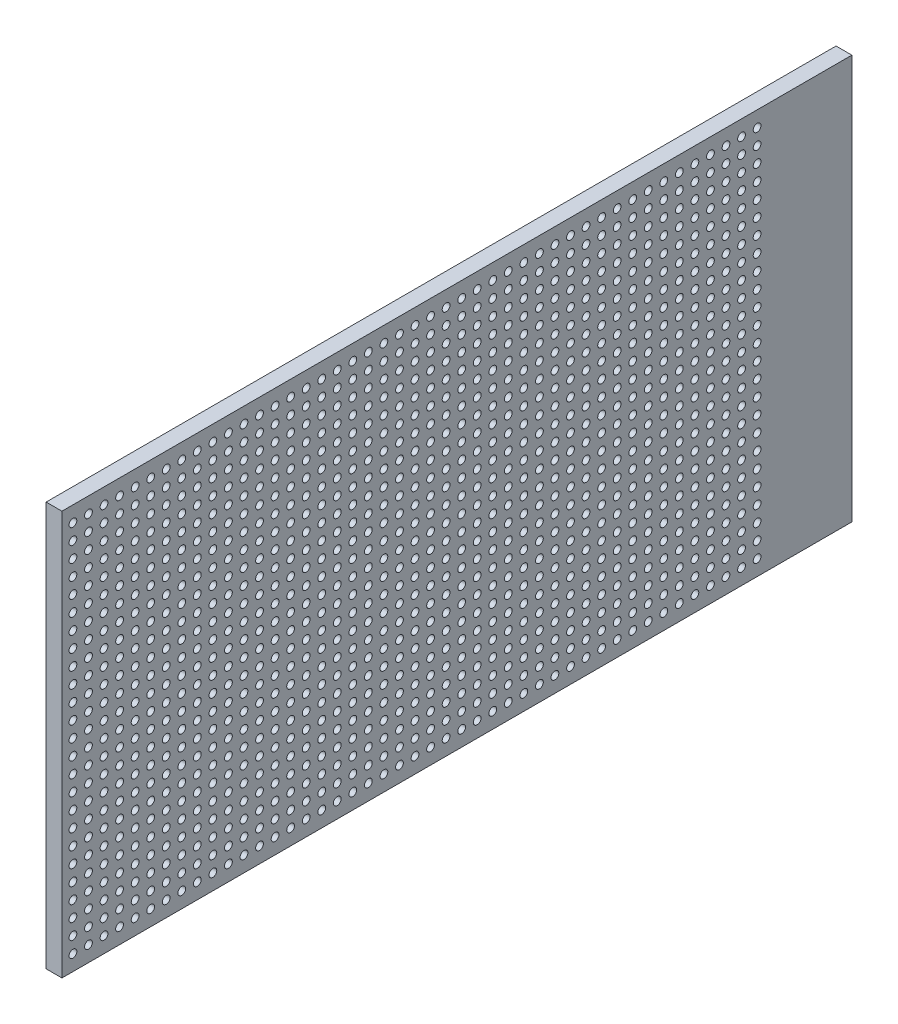
SolidWorks part; units mm, degrees
ref_plane "Спереди" through (0, 0, 0) normal (0, 0, 1) x (1, 0, 0)
ref_plane "Сверху" through (0, 0, 0) normal (0, 1, 0) x (1, 0, 0)
ref_plane "Справа" through (0, 0, 0) normal (1, 0, 0) x (0, 0, -1)
sketch "Эскиз2" plane through (0, 0, 0) normal (1, 0, 0) x (0, 0, -1)
  line L1 (1.4683, 0) -> (255.4683, 0)
  line L2 (1.4683, 0) -> (1.4683, 130)
  line L3 (1.4683, 130) -> (255.4683, 130)
  line L4 (255.4683, 0) -> (255.4683, 130)
  circle A0 centre (5, 5) radius 1.25
  circle A1 centre (10, 5) radius 1.25
  circle A2 centre (15, 5) radius 1.25
  circle A3 centre (20, 5) radius 1.25
  circle A4 centre (25, 5) radius 1.25
  circle A5 centre (30, 5) radius 1.25
  circle A6 centre (10, 10) radius 1.25
  circle A7 centre (15, 10) radius 1.25
  circle A8 centre (20, 10) radius 1.25
  circle A9 centre (25, 10) radius 1.25
  circle A10 centre (30, 10) radius 1.25
  circle A11 centre (10, 15) radius 1.25
  circle A12 centre (15, 15) radius 1.25
  circle A13 centre (20, 15) radius 1.25
  circle A14 centre (25, 15) radius 1.25
  circle A15 centre (30, 15) radius 1.25
  circle A16 centre (10, 20) radius 1.25
  circle A17 centre (15, 20) radius 1.25
  circle A18 centre (20, 20) radius 1.25
  circle A19 centre (25, 20) radius 1.25
  circle A20 centre (30, 20) radius 1.25
  circle A21 centre (10, 25) radius 1.25
  circle A22 centre (15, 25) radius 1.25
  circle A23 centre (20, 25) radius 1.25
  circle A24 centre (25, 25) radius 1.25
  circle A25 centre (30, 25) radius 1.25
  circle A26 centre (5, 10) radius 1.25
  circle A27 centre (5, 15) radius 1.25
  circle A28 centre (5, 20) radius 1.25
  circle A29 centre (5, 25) radius 1.25
  circle A30 centre (5, 30) radius 1.25
  circle A31 centre (10, 30) radius 1.25
  circle A32 centre (15, 30) radius 1.25
  circle A33 centre (20, 30) radius 1.25
  circle A34 centre (25, 30) radius 1.25
  circle A35 centre (30, 30) radius 1.25
  circle A36 centre (5, 35) radius 1.25
  circle A37 centre (10, 35) radius 1.25
  circle A38 centre (15, 35) radius 1.25
  circle A39 centre (20, 35) radius 1.25
  circle A40 centre (25, 35) radius 1.25
  circle A41 centre (30, 35) radius 1.25
  circle A42 centre (5, 40) radius 1.25
  circle A43 centre (10, 40) radius 1.25
  circle A44 centre (15, 40) radius 1.25
  circle A45 centre (20, 40) radius 1.25
  circle A46 centre (25, 40) radius 1.25
  circle A47 centre (30, 40) radius 1.25
  circle A48 centre (5, 45) radius 1.25
  circle A49 centre (10, 45) radius 1.25
  circle A50 centre (15, 45) radius 1.25
  circle A51 centre (20, 45) radius 1.25
  circle A52 centre (25, 45) radius 1.25
  circle A53 centre (30, 45) radius 1.25
  circle A54 centre (5, 50) radius 1.25
  circle A55 centre (10, 50) radius 1.25
  circle A56 centre (15, 50) radius 1.25
  circle A57 centre (20, 50) radius 1.25
  circle A58 centre (25, 50) radius 1.25
  circle A59 centre (30, 50) radius 1.25
  circle A60 centre (5, 55) radius 1.25
  circle A61 centre (10, 55) radius 1.25
  circle A62 centre (15, 55) radius 1.25
  circle A63 centre (20, 55) radius 1.25
  circle A64 centre (25, 55) radius 1.25
  circle A65 centre (30, 55) radius 1.25
  circle A66 centre (5, 60) radius 1.25
  circle A67 centre (10, 60) radius 1.25
  circle A68 centre (15, 60) radius 1.25
  circle A69 centre (20, 60) radius 1.25
  circle A70 centre (25, 60) radius 1.25
  circle A71 centre (30, 60) radius 1.25
  circle A72 centre (5, 65) radius 1.25
  circle A73 centre (10, 65) radius 1.25
  circle A74 centre (15, 65) radius 1.25
  circle A75 centre (20, 65) radius 1.25
  circle A76 centre (25, 65) radius 1.25
  circle A77 centre (30, 65) radius 1.25
  circle A78 centre (5, 70) radius 1.25
  circle A79 centre (10, 70) radius 1.25
  circle A80 centre (15, 70) radius 1.25
  circle A81 centre (20, 70) radius 1.25
  circle A82 centre (25, 70) radius 1.25
  circle A83 centre (30, 70) radius 1.25
  circle A84 centre (5, 75) radius 1.25
  circle A85 centre (10, 75) radius 1.25
  circle A86 centre (15, 75) radius 1.25
  circle A87 centre (20, 75) radius 1.25
  circle A88 centre (25, 75) radius 1.25
  circle A89 centre (30, 75) radius 1.25
  circle A90 centre (5, 80) radius 1.25
  circle A91 centre (10, 80) radius 1.25
  circle A92 centre (15, 80) radius 1.25
  circle A93 centre (20, 80) radius 1.25
  circle A94 centre (25, 80) radius 1.25
  circle A95 centre (30, 80) radius 1.25
  circle A96 centre (5, 85) radius 1.25
  circle A97 centre (10, 85) radius 1.25
  circle A98 centre (15, 85) radius 1.25
  circle A99 centre (20, 85) radius 1.25
  circle A100 centre (25, 85) radius 1.25
  circle A101 centre (30, 85) radius 1.25
  circle A102 centre (5, 90) radius 1.25
  circle A103 centre (10, 90) radius 1.25
  circle A104 centre (15, 90) radius 1.25
  circle A105 centre (20, 90) radius 1.25
  circle A106 centre (25, 90) radius 1.25
  circle A107 centre (30, 90) radius 1.25
  circle A108 centre (5, 95) radius 1.25
  circle A109 centre (10, 95) radius 1.25
  circle A110 centre (15, 95) radius 1.25
  circle A111 centre (20, 95) radius 1.25
  circle A112 centre (25, 95) radius 1.25
  circle A113 centre (30, 95) radius 1.25
  circle A114 centre (5, 100) radius 1.25
  circle A115 centre (10, 100) radius 1.25
  circle A116 centre (15, 100) radius 1.25
  circle A117 centre (20, 100) radius 1.25
  circle A118 centre (25, 100) radius 1.25
  circle A119 centre (30, 100) radius 1.25
  circle A120 centre (5, 105) radius 1.25
  circle A121 centre (10, 105) radius 1.25
  circle A122 centre (15, 105) radius 1.25
  circle A123 centre (20, 105) radius 1.25
  circle A124 centre (25, 105) radius 1.25
  circle A125 centre (30, 105) radius 1.25
  circle A126 centre (5, 110) radius 1.25
  circle A127 centre (10, 110) radius 1.25
  circle A128 centre (15, 110) radius 1.25
  circle A129 centre (20, 110) radius 1.25
  circle A130 centre (25, 110) radius 1.25
  circle A131 centre (30, 110) radius 1.25
  circle A132 centre (5, 115) radius 1.25
  circle A133 centre (10, 115) radius 1.25
  circle A134 centre (15, 115) radius 1.25
  circle A135 centre (20, 115) radius 1.25
  circle A136 centre (25, 115) radius 1.25
  circle A137 centre (30, 115) radius 1.25
  circle A138 centre (5, 120) radius 1.25
  circle A139 centre (10, 120) radius 1.25
  circle A140 centre (15, 120) radius 1.25
  circle A141 centre (20, 120) radius 1.25
  circle A142 centre (25, 120) radius 1.25
  circle A143 centre (30, 120) radius 1.25
  circle A144 centre (5, 125) radius 1.25
  circle A145 centre (10, 125) radius 1.25
  circle A146 centre (15, 125) radius 1.25
  circle A147 centre (20, 125) radius 1.25
  circle A148 centre (25, 125) radius 1.25
  circle A149 centre (30, 125) radius 1.25
  circle A150 centre (35, 5) radius 1.25
  circle A151 centre (40, 5) radius 1.25
  circle A152 centre (45, 5) radius 1.25
  circle A153 centre (50, 5) radius 1.25
  circle A154 centre (55, 5) radius 1.25
  circle A155 centre (60, 5) radius 1.25
  circle A156 centre (65, 5) radius 1.25
  circle A157 centre (70, 5) radius 1.25
  circle A158 centre (75, 5) radius 1.25
  circle A159 centre (80, 5) radius 1.25
  circle A160 centre (85, 5) radius 1.25
  circle A161 centre (90, 5) radius 1.25
  circle A162 centre (95, 5) radius 1.25
  circle A163 centre (100, 5) radius 1.25
  circle A164 centre (105, 5) radius 1.25
  circle A165 centre (110, 5) radius 1.25
  circle A166 centre (35, 10) radius 1.25
  circle A167 centre (40, 10) radius 1.25
  circle A168 centre (45, 10) radius 1.25
  circle A169 centre (50, 10) radius 1.25
  circle A170 centre (55, 10) radius 1.25
  circle A171 centre (60, 10) radius 1.25
  circle A172 centre (65, 10) radius 1.25
  circle A173 centre (70, 10) radius 1.25
  circle A174 centre (75, 10) radius 1.25
  circle A175 centre (80, 10) radius 1.25
  circle A176 centre (85, 10) radius 1.25
  circle A177 centre (90, 10) radius 1.25
  circle A178 centre (95, 10) radius 1.25
  circle A179 centre (100, 10) radius 1.25
  circle A180 centre (105, 10) radius 1.25
  circle A181 centre (110, 10) radius 1.25
  circle A182 centre (35, 15) radius 1.25
  circle A183 centre (40, 15) radius 1.25
  circle A184 centre (45, 15) radius 1.25
  circle A185 centre (50, 15) radius 1.25
  circle A186 centre (55, 15) radius 1.25
  circle A187 centre (60, 15) radius 1.25
  circle A188 centre (65, 15) radius 1.25
  circle A189 centre (70, 15) radius 1.25
  circle A190 centre (75, 15) radius 1.25
  circle A191 centre (80, 15) radius 1.25
  circle A192 centre (85, 15) radius 1.25
  circle A193 centre (90, 15) radius 1.25
  circle A194 centre (95, 15) radius 1.25
  circle A195 centre (100, 15) radius 1.25
  circle A196 centre (105, 15) radius 1.25
  circle A197 centre (110, 15) radius 1.25
  circle A198 centre (35, 20) radius 1.25
  circle A199 centre (40, 20) radius 1.25
  circle A200 centre (45, 20) radius 1.25
  circle A201 centre (50, 20) radius 1.25
  circle A202 centre (55, 20) radius 1.25
  circle A203 centre (60, 20) radius 1.25
  circle A204 centre (65, 20) radius 1.25
  circle A205 centre (70, 20) radius 1.25
  circle A206 centre (75, 20) radius 1.25
  circle A207 centre (80, 20) radius 1.25
  circle A208 centre (85, 20) radius 1.25
  circle A209 centre (90, 20) radius 1.25
  circle A210 centre (95, 20) radius 1.25
  circle A211 centre (100, 20) radius 1.25
  circle A212 centre (105, 20) radius 1.25
  circle A213 centre (110, 20) radius 1.25
  circle A214 centre (35, 25) radius 1.25
  circle A215 centre (40, 25) radius 1.25
  circle A216 centre (45, 25) radius 1.25
  circle A217 centre (50, 25) radius 1.25
  circle A218 centre (55, 25) radius 1.25
  circle A219 centre (60, 25) radius 1.25
  circle A220 centre (65, 25) radius 1.25
  circle A221 centre (70, 25) radius 1.25
  circle A222 centre (75, 25) radius 1.25
  circle A223 centre (80, 25) radius 1.25
  circle A224 centre (85, 25) radius 1.25
  circle A225 centre (90, 25) radius 1.25
  circle A226 centre (95, 25) radius 1.25
  circle A227 centre (100, 25) radius 1.25
  circle A228 centre (105, 25) radius 1.25
  circle A229 centre (110, 25) radius 1.25
  circle A230 centre (35, 30) radius 1.25
  circle A231 centre (40, 30) radius 1.25
  circle A232 centre (45, 30) radius 1.25
  circle A233 centre (50, 30) radius 1.25
  circle A234 centre (55, 30) radius 1.25
  circle A235 centre (60, 30) radius 1.25
  circle A236 centre (65, 30) radius 1.25
  circle A237 centre (70, 30) radius 1.25
  circle A238 centre (75, 30) radius 1.25
  circle A239 centre (80, 30) radius 1.25
  circle A240 centre (85, 30) radius 1.25
  circle A241 centre (90, 30) radius 1.25
  circle A242 centre (95, 30) radius 1.25
  circle A243 centre (100, 30) radius 1.25
  circle A244 centre (105, 30) radius 1.25
  circle A245 centre (110, 30) radius 1.25
  circle A246 centre (35, 35) radius 1.25
  circle A247 centre (40, 35) radius 1.25
  circle A248 centre (45, 35) radius 1.25
  circle A249 centre (50, 35) radius 1.25
  circle A250 centre (55, 35) radius 1.25
  circle A251 centre (60, 35) radius 1.25
  circle A252 centre (65, 35) radius 1.25
  circle A253 centre (70, 35) radius 1.25
  circle A254 centre (75, 35) radius 1.25
  circle A255 centre (80, 35) radius 1.25
  circle A256 centre (85, 35) radius 1.25
  circle A257 centre (90, 35) radius 1.25
  circle A258 centre (95, 35) radius 1.25
  circle A259 centre (100, 35) radius 1.25
  circle A260 centre (105, 35) radius 1.25
  circle A261 centre (110, 35) radius 1.25
  circle A262 centre (35, 40) radius 1.25
  circle A263 centre (40, 40) radius 1.25
  circle A264 centre (45, 40) radius 1.25
  circle A265 centre (50, 40) radius 1.25
  circle A266 centre (55, 40) radius 1.25
  circle A267 centre (60, 40) radius 1.25
  circle A268 centre (65, 40) radius 1.25
  circle A269 centre (70, 40) radius 1.25
  circle A270 centre (75, 40) radius 1.25
  circle A271 centre (80, 40) radius 1.25
  circle A272 centre (85, 40) radius 1.25
  circle A273 centre (90, 40) radius 1.25
  circle A274 centre (95, 40) radius 1.25
  circle A275 centre (100, 40) radius 1.25
  circle A276 centre (105, 40) radius 1.25
  circle A277 centre (110, 40) radius 1.25
  circle A278 centre (35, 45) radius 1.25
  circle A279 centre (40, 45) radius 1.25
  circle A280 centre (45, 45) radius 1.25
  circle A281 centre (50, 45) radius 1.25
  circle A282 centre (55, 45) radius 1.25
  circle A283 centre (60, 45) radius 1.25
  circle A284 centre (65, 45) radius 1.25
  circle A285 centre (70, 45) radius 1.25
  circle A286 centre (75, 45) radius 1.25
  circle A287 centre (80, 45) radius 1.25
  circle A288 centre (85, 45) radius 1.25
  circle A289 centre (90, 45) radius 1.25
  circle A290 centre (95, 45) radius 1.25
  circle A291 centre (100, 45) radius 1.25
  circle A292 centre (105, 45) radius 1.25
  circle A293 centre (110, 45) radius 1.25
  circle A294 centre (35, 50) radius 1.25
  circle A295 centre (40, 50) radius 1.25
  circle A296 centre (45, 50) radius 1.25
  circle A297 centre (50, 50) radius 1.25
  circle A298 centre (55, 50) radius 1.25
  circle A299 centre (60, 50) radius 1.25
  circle A300 centre (65, 50) radius 1.25
  circle A301 centre (70, 50) radius 1.25
  circle A302 centre (75, 50) radius 1.25
  circle A303 centre (80, 50) radius 1.25
  circle A304 centre (85, 50) radius 1.25
  circle A305 centre (90, 50) radius 1.25
  circle A306 centre (95, 50) radius 1.25
  circle A307 centre (100, 50) radius 1.25
  circle A308 centre (105, 50) radius 1.25
  circle A309 centre (110, 50) radius 1.25
  circle A310 centre (35, 55) radius 1.25
  circle A311 centre (40, 55) radius 1.25
  circle A312 centre (45, 55) radius 1.25
  circle A313 centre (50, 55) radius 1.25
  circle A314 centre (55, 55) radius 1.25
  circle A315 centre (60, 55) radius 1.25
  circle A316 centre (65, 55) radius 1.25
  circle A317 centre (70, 55) radius 1.25
  circle A318 centre (75, 55) radius 1.25
  circle A319 centre (80, 55) radius 1.25
  circle A320 centre (85, 55) radius 1.25
  circle A321 centre (90, 55) radius 1.25
  circle A322 centre (95, 55) radius 1.25
  circle A323 centre (100, 55) radius 1.25
  circle A324 centre (105, 55) radius 1.25
  circle A325 centre (110, 55) radius 1.25
  circle A326 centre (35, 60) radius 1.25
  circle A327 centre (40, 60) radius 1.25
  circle A328 centre (45, 60) radius 1.25
  circle A329 centre (50, 60) radius 1.25
  circle A330 centre (55, 60) radius 1.25
  circle A331 centre (60, 60) radius 1.25
  circle A332 centre (65, 60) radius 1.25
  circle A333 centre (70, 60) radius 1.25
  circle A334 centre (75, 60) radius 1.25
  circle A335 centre (80, 60) radius 1.25
  circle A336 centre (85, 60) radius 1.25
  circle A337 centre (90, 60) radius 1.25
  circle A338 centre (95, 60) radius 1.25
  circle A339 centre (100, 60) radius 1.25
  circle A340 centre (105, 60) radius 1.25
  circle A341 centre (110, 60) radius 1.25
  circle A342 centre (35, 65) radius 1.25
  circle A343 centre (40, 65) radius 1.25
  circle A344 centre (45, 65) radius 1.25
  circle A345 centre (50, 65) radius 1.25
  circle A346 centre (55, 65) radius 1.25
  circle A347 centre (60, 65) radius 1.25
  circle A348 centre (65, 65) radius 1.25
  circle A349 centre (70, 65) radius 1.25
  circle A350 centre (75, 65) radius 1.25
  circle A351 centre (80, 65) radius 1.25
  circle A352 centre (85, 65) radius 1.25
  circle A353 centre (90, 65) radius 1.25
  circle A354 centre (95, 65) radius 1.25
  circle A355 centre (100, 65) radius 1.25
  circle A356 centre (105, 65) radius 1.25
  circle A357 centre (110, 65) radius 1.25
  circle A358 centre (35, 70) radius 1.25
  circle A359 centre (40, 70) radius 1.25
  circle A360 centre (45, 70) radius 1.25
  circle A361 centre (50, 70) radius 1.25
  circle A362 centre (55, 70) radius 1.25
  circle A363 centre (60, 70) radius 1.25
  circle A364 centre (65, 70) radius 1.25
  circle A365 centre (70, 70) radius 1.25
  circle A366 centre (75, 70) radius 1.25
  circle A367 centre (80, 70) radius 1.25
  circle A368 centre (85, 70) radius 1.25
  circle A369 centre (90, 70) radius 1.25
  circle A370 centre (95, 70) radius 1.25
  circle A371 centre (100, 70) radius 1.25
  circle A372 centre (105, 70) radius 1.25
  circle A373 centre (110, 70) radius 1.25
  circle A374 centre (35, 75) radius 1.25
  circle A375 centre (40, 75) radius 1.25
  circle A376 centre (45, 75) radius 1.25
  circle A377 centre (50, 75) radius 1.25
  circle A378 centre (55, 75) radius 1.25
  circle A379 centre (60, 75) radius 1.25
  circle A380 centre (65, 75) radius 1.25
  circle A381 centre (70, 75) radius 1.25
  circle A382 centre (75, 75) radius 1.25
  circle A383 centre (80, 75) radius 1.25
  circle A384 centre (85, 75) radius 1.25
  circle A385 centre (90, 75) radius 1.25
  circle A386 centre (95, 75) radius 1.25
  circle A387 centre (100, 75) radius 1.25
  circle A388 centre (105, 75) radius 1.25
  circle A389 centre (110, 75) radius 1.25
  circle A390 centre (35, 80) radius 1.25
  circle A391 centre (40, 80) radius 1.25
  circle A392 centre (45, 80) radius 1.25
  circle A393 centre (50, 80) radius 1.25
  circle A394 centre (55, 80) radius 1.25
  circle A395 centre (60, 80) radius 1.25
  circle A396 centre (65, 80) radius 1.25
  circle A397 centre (70, 80) radius 1.25
  circle A398 centre (75, 80) radius 1.25
  circle A399 centre (80, 80) radius 1.25
  circle A400 centre (85, 80) radius 1.25
  circle A401 centre (90, 80) radius 1.25
  circle A402 centre (95, 80) radius 1.25
  circle A403 centre (100, 80) radius 1.25
  circle A404 centre (105, 80) radius 1.25
  circle A405 centre (110, 80) radius 1.25
  circle A406 centre (35, 85) radius 1.25
  circle A407 centre (40, 85) radius 1.25
  circle A408 centre (45, 85) radius 1.25
  circle A409 centre (50, 85) radius 1.25
  circle A410 centre (55, 85) radius 1.25
  circle A411 centre (60, 85) radius 1.25
  circle A412 centre (65, 85) radius 1.25
  circle A413 centre (70, 85) radius 1.25
  circle A414 centre (75, 85) radius 1.25
  circle A415 centre (80, 85) radius 1.25
  circle A416 centre (85, 85) radius 1.25
  circle A417 centre (90, 85) radius 1.25
  circle A418 centre (95, 85) radius 1.25
  circle A419 centre (100, 85) radius 1.25
  circle A420 centre (105, 85) radius 1.25
  circle A421 centre (110, 85) radius 1.25
  circle A422 centre (35, 90) radius 1.25
  circle A423 centre (40, 90) radius 1.25
  circle A424 centre (45, 90) radius 1.25
  circle A425 centre (50, 90) radius 1.25
  circle A426 centre (55, 90) radius 1.25
  circle A427 centre (60, 90) radius 1.25
  circle A428 centre (65, 90) radius 1.25
  circle A429 centre (70, 90) radius 1.25
  circle A430 centre (75, 90) radius 1.25
  circle A431 centre (80, 90) radius 1.25
  circle A432 centre (85, 90) radius 1.25
  circle A433 centre (90, 90) radius 1.25
  circle A434 centre (95, 90) radius 1.25
  circle A435 centre (100, 90) radius 1.25
  circle A436 centre (105, 90) radius 1.25
  circle A437 centre (110, 90) radius 1.25
  circle A438 centre (35, 95) radius 1.25
  circle A439 centre (40, 95) radius 1.25
  circle A440 centre (45, 95) radius 1.25
  circle A441 centre (50, 95) radius 1.25
  circle A442 centre (55, 95) radius 1.25
  circle A443 centre (60, 95) radius 1.25
  circle A444 centre (65, 95) radius 1.25
  circle A445 centre (70, 95) radius 1.25
  circle A446 centre (75, 95) radius 1.25
  circle A447 centre (80, 95) radius 1.25
  circle A448 centre (85, 95) radius 1.25
  circle A449 centre (90, 95) radius 1.25
  circle A450 centre (95, 95) radius 1.25
  circle A451 centre (100, 95) radius 1.25
  circle A452 centre (105, 95) radius 1.25
  circle A453 centre (110, 95) radius 1.25
  circle A454 centre (35, 100) radius 1.25
  circle A455 centre (40, 100) radius 1.25
  circle A456 centre (45, 100) radius 1.25
  circle A457 centre (50, 100) radius 1.25
  circle A458 centre (55, 100) radius 1.25
  circle A459 centre (60, 100) radius 1.25
  circle A460 centre (65, 100) radius 1.25
  circle A461 centre (70, 100) radius 1.25
  circle A462 centre (75, 100) radius 1.25
  circle A463 centre (80, 100) radius 1.25
  circle A464 centre (85, 100) radius 1.25
  circle A465 centre (90, 100) radius 1.25
  circle A466 centre (95, 100) radius 1.25
  circle A467 centre (100, 100) radius 1.25
  circle A468 centre (105, 100) radius 1.25
  circle A469 centre (110, 100) radius 1.25
  circle A470 centre (35, 105) radius 1.25
  circle A471 centre (40, 105) radius 1.25
  circle A472 centre (45, 105) radius 1.25
  circle A473 centre (50, 105) radius 1.25
  circle A474 centre (55, 105) radius 1.25
  circle A475 centre (60, 105) radius 1.25
  circle A476 centre (65, 105) radius 1.25
  circle A477 centre (70, 105) radius 1.25
  circle A478 centre (75, 105) radius 1.25
  circle A479 centre (80, 105) radius 1.25
  circle A480 centre (85, 105) radius 1.25
  circle A481 centre (90, 105) radius 1.25
  circle A482 centre (95, 105) radius 1.25
  circle A483 centre (100, 105) radius 1.25
  circle A484 centre (105, 105) radius 1.25
  circle A485 centre (110, 105) radius 1.25
  circle A486 centre (35, 110) radius 1.25
  circle A487 centre (40, 110) radius 1.25
  circle A488 centre (45, 110) radius 1.25
  circle A489 centre (50, 110) radius 1.25
  circle A490 centre (55, 110) radius 1.25
  circle A491 centre (60, 110) radius 1.25
  circle A492 centre (65, 110) radius 1.25
  circle A493 centre (70, 110) radius 1.25
  circle A494 centre (75, 110) radius 1.25
  circle A495 centre (80, 110) radius 1.25
  circle A496 centre (85, 110) radius 1.25
  circle A497 centre (90, 110) radius 1.25
  circle A498 centre (95, 110) radius 1.25
  circle A499 centre (100, 110) radius 1.25
  circle A500 centre (105, 110) radius 1.25
  circle A501 centre (110, 110) radius 1.25
  circle A502 centre (35, 115) radius 1.25
  circle A503 centre (40, 115) radius 1.25
  circle A504 centre (45, 115) radius 1.25
  circle A505 centre (50, 115) radius 1.25
  circle A506 centre (55, 115) radius 1.25
  circle A507 centre (60, 115) radius 1.25
  circle A508 centre (65, 115) radius 1.25
  circle A509 centre (70, 115) radius 1.25
  circle A510 centre (75, 115) radius 1.25
  circle A511 centre (80, 115) radius 1.25
  circle A512 centre (85, 115) radius 1.25
  circle A513 centre (90, 115) radius 1.25
  circle A514 centre (95, 115) radius 1.25
  circle A515 centre (100, 115) radius 1.25
  circle A516 centre (105, 115) radius 1.25
  circle A517 centre (110, 115) radius 1.25
  circle A518 centre (35, 120) radius 1.25
  circle A519 centre (40, 120) radius 1.25
  circle A520 centre (45, 120) radius 1.25
  circle A521 centre (50, 120) radius 1.25
  circle A522 centre (55, 120) radius 1.25
  circle A523 centre (60, 120) radius 1.25
  circle A524 centre (65, 120) radius 1.25
  circle A525 centre (70, 120) radius 1.25
  circle A526 centre (75, 120) radius 1.25
  circle A527 centre (80, 120) radius 1.25
  circle A528 centre (85, 120) radius 1.25
  circle A529 centre (90, 120) radius 1.25
  circle A530 centre (95, 120) radius 1.25
  circle A531 centre (100, 120) radius 1.25
  circle A532 centre (105, 120) radius 1.25
  circle A533 centre (110, 120) radius 1.25
  circle A534 centre (35, 125) radius 1.25
  circle A535 centre (40, 125) radius 1.25
  circle A536 centre (45, 125) radius 1.25
  circle A537 centre (50, 125) radius 1.25
  circle A538 centre (55, 125) radius 1.25
  circle A539 centre (60, 125) radius 1.25
  circle A540 centre (65, 125) radius 1.25
  circle A541 centre (70, 125) radius 1.25
  circle A542 centre (75, 125) radius 1.25
  circle A543 centre (80, 125) radius 1.25
  circle A544 centre (85, 125) radius 1.25
  circle A545 centre (90, 125) radius 1.25
  circle A546 centre (95, 125) radius 1.25
  circle A547 centre (100, 125) radius 1.25
  circle A548 centre (105, 125) radius 1.25
  circle A549 centre (110, 125) radius 1.25
  circle A550 centre (115, 5) radius 1.25
  circle A551 centre (120, 5) radius 1.25
  circle A552 centre (125, 5) radius 1.25
  circle A553 centre (130, 5) radius 1.25
  circle A554 centre (135, 5) radius 1.25
  circle A555 centre (140, 5) radius 1.25
  circle A556 centre (145, 5) radius 1.25
  circle A557 centre (150, 5) radius 1.25
  circle A558 centre (155, 5) radius 1.25
  circle A559 centre (160, 5) radius 1.25
  circle A560 centre (165, 5) radius 1.25
  circle A561 centre (170, 5) radius 1.25
  circle A562 centre (175, 5) radius 1.25
  circle A563 centre (115, 10) radius 1.25
  circle A564 centre (120, 10) radius 1.25
  circle A565 centre (125, 10) radius 1.25
  circle A566 centre (130, 10) radius 1.25
  circle A567 centre (135, 10) radius 1.25
  circle A568 centre (140, 10) radius 1.25
  circle A569 centre (145, 10) radius 1.25
  circle A570 centre (150, 10) radius 1.25
  circle A571 centre (155, 10) radius 1.25
  circle A572 centre (160, 10) radius 1.25
  circle A573 centre (165, 10) radius 1.25
  circle A574 centre (170, 10) radius 1.25
  circle A575 centre (175, 10) radius 1.25
  circle A576 centre (115, 15) radius 1.25
  circle A577 centre (120, 15) radius 1.25
  circle A578 centre (125, 15) radius 1.25
  circle A579 centre (130, 15) radius 1.25
  circle A580 centre (135, 15) radius 1.25
  circle A581 centre (140, 15) radius 1.25
  circle A582 centre (145, 15) radius 1.25
  circle A583 centre (150, 15) radius 1.25
  circle A584 centre (155, 15) radius 1.25
  circle A585 centre (160, 15) radius 1.25
  circle A586 centre (165, 15) radius 1.25
  circle A587 centre (170, 15) radius 1.25
  circle A588 centre (175, 15) radius 1.25
  circle A589 centre (115, 20) radius 1.25
  circle A590 centre (120, 20) radius 1.25
  circle A591 centre (125, 20) radius 1.25
  circle A592 centre (130, 20) radius 1.25
  circle A593 centre (135, 20) radius 1.25
  circle A594 centre (140, 20) radius 1.25
  circle A595 centre (145, 20) radius 1.25
  circle A596 centre (150, 20) radius 1.25
  circle A597 centre (155, 20) radius 1.25
  circle A598 centre (160, 20) radius 1.25
  circle A599 centre (165, 20) radius 1.25
  circle A600 centre (170, 20) radius 1.25
  circle A601 centre (175, 20) radius 1.25
  circle A602 centre (115, 25) radius 1.25
  circle A603 centre (120, 25) radius 1.25
  circle A604 centre (125, 25) radius 1.25
  circle A605 centre (130, 25) radius 1.25
  circle A606 centre (135, 25) radius 1.25
  circle A607 centre (140, 25) radius 1.25
  circle A608 centre (145, 25) radius 1.25
  circle A609 centre (150, 25) radius 1.25
  circle A610 centre (155, 25) radius 1.25
  circle A611 centre (160, 25) radius 1.25
  circle A612 centre (165, 25) radius 1.25
  circle A613 centre (170, 25) radius 1.25
  circle A614 centre (175, 25) radius 1.25
  circle A615 centre (115, 30) radius 1.25
  circle A616 centre (120, 30) radius 1.25
  circle A617 centre (125, 30) radius 1.25
  circle A618 centre (130, 30) radius 1.25
  circle A619 centre (135, 30) radius 1.25
  circle A620 centre (140, 30) radius 1.25
  circle A621 centre (145, 30) radius 1.25
  circle A622 centre (150, 30) radius 1.25
  circle A623 centre (155, 30) radius 1.25
  circle A624 centre (160, 30) radius 1.25
  circle A625 centre (165, 30) radius 1.25
  circle A626 centre (170, 30) radius 1.25
  circle A627 centre (175, 30) radius 1.25
  circle A628 centre (115, 35) radius 1.25
  circle A629 centre (120, 35) radius 1.25
  circle A630 centre (125, 35) radius 1.25
  circle A631 centre (130, 35) radius 1.25
  circle A632 centre (135, 35) radius 1.25
  circle A633 centre (140, 35) radius 1.25
  circle A634 centre (145, 35) radius 1.25
  circle A635 centre (150, 35) radius 1.25
  circle A636 centre (155, 35) radius 1.25
  circle A637 centre (160, 35) radius 1.25
  circle A638 centre (165, 35) radius 1.25
  circle A639 centre (170, 35) radius 1.25
  circle A640 centre (175, 35) radius 1.25
  circle A641 centre (115, 40) radius 1.25
  circle A642 centre (120, 40) radius 1.25
  circle A643 centre (125, 40) radius 1.25
  circle A644 centre (130, 40) radius 1.25
  circle A645 centre (135, 40) radius 1.25
  circle A646 centre (140, 40) radius 1.25
  circle A647 centre (145, 40) radius 1.25
  circle A648 centre (150, 40) radius 1.25
  circle A649 centre (155, 40) radius 1.25
  circle A650 centre (160, 40) radius 1.25
  circle A651 centre (165, 40) radius 1.25
  circle A652 centre (170, 40) radius 1.25
  circle A653 centre (175, 40) radius 1.25
  circle A654 centre (115, 45) radius 1.25
  circle A655 centre (120, 45) radius 1.25
  circle A656 centre (125, 45) radius 1.25
  circle A657 centre (130, 45) radius 1.25
  circle A658 centre (135, 45) radius 1.25
  circle A659 centre (140, 45) radius 1.25
  circle A660 centre (145, 45) radius 1.25
  circle A661 centre (150, 45) radius 1.25
  circle A662 centre (155, 45) radius 1.25
  circle A663 centre (160, 45) radius 1.25
  circle A664 centre (165, 45) radius 1.25
  circle A665 centre (170, 45) radius 1.25
  circle A666 centre (175, 45) radius 1.25
  circle A667 centre (115, 50) radius 1.25
  circle A668 centre (120, 50) radius 1.25
  circle A669 centre (125, 50) radius 1.25
  circle A670 centre (130, 50) radius 1.25
  circle A671 centre (135, 50) radius 1.25
  circle A672 centre (140, 50) radius 1.25
  circle A673 centre (145, 50) radius 1.25
  circle A674 centre (150, 50) radius 1.25
  circle A675 centre (155, 50) radius 1.25
  circle A676 centre (160, 50) radius 1.25
  circle A677 centre (165, 50) radius 1.25
  circle A678 centre (170, 50) radius 1.25
  circle A679 centre (175, 50) radius 1.25
  circle A680 centre (115, 55) radius 1.25
  circle A681 centre (120, 55) radius 1.25
  circle A682 centre (125, 55) radius 1.25
  circle A683 centre (130, 55) radius 1.25
  circle A684 centre (135, 55) radius 1.25
  circle A685 centre (140, 55) radius 1.25
  circle A686 centre (145, 55) radius 1.25
  circle A687 centre (150, 55) radius 1.25
  circle A688 centre (155, 55) radius 1.25
  circle A689 centre (160, 55) radius 1.25
  circle A690 centre (165, 55) radius 1.25
  circle A691 centre (170, 55) radius 1.25
  circle A692 centre (175, 55) radius 1.25
  circle A693 centre (115, 60) radius 1.25
  circle A694 centre (120, 60) radius 1.25
  circle A695 centre (125, 60) radius 1.25
  circle A696 centre (130, 60) radius 1.25
  circle A697 centre (135, 60) radius 1.25
  circle A698 centre (140, 60) radius 1.25
  circle A699 centre (145, 60) radius 1.25
  circle A700 centre (150, 60) radius 1.25
  circle A701 centre (155, 60) radius 1.25
  circle A702 centre (160, 60) radius 1.25
  circle A703 centre (165, 60) radius 1.25
  circle A704 centre (170, 60) radius 1.25
  circle A705 centre (175, 60) radius 1.25
  circle A706 centre (115, 65) radius 1.25
  circle A707 centre (120, 65) radius 1.25
  circle A708 centre (125, 65) radius 1.25
  circle A709 centre (130, 65) radius 1.25
  circle A710 centre (135, 65) radius 1.25
  circle A711 centre (140, 65) radius 1.25
  circle A712 centre (145, 65) radius 1.25
  circle A713 centre (150, 65) radius 1.25
  circle A714 centre (155, 65) radius 1.25
  circle A715 centre (160, 65) radius 1.25
  circle A716 centre (165, 65) radius 1.25
  circle A717 centre (170, 65) radius 1.25
  circle A718 centre (175, 65) radius 1.25
  circle A719 centre (115, 70) radius 1.25
  circle A720 centre (120, 70) radius 1.25
  circle A721 centre (125, 70) radius 1.25
  circle A722 centre (130, 70) radius 1.25
  circle A723 centre (135, 70) radius 1.25
  circle A724 centre (140, 70) radius 1.25
  circle A725 centre (145, 70) radius 1.25
  circle A726 centre (150, 70) radius 1.25
  circle A727 centre (155, 70) radius 1.25
  circle A728 centre (160, 70) radius 1.25
  circle A729 centre (165, 70) radius 1.25
  circle A730 centre (170, 70) radius 1.25
  circle A731 centre (175, 70) radius 1.25
  circle A732 centre (115, 75) radius 1.25
  circle A733 centre (120, 75) radius 1.25
  circle A734 centre (125, 75) radius 1.25
  circle A735 centre (130, 75) radius 1.25
  circle A736 centre (135, 75) radius 1.25
  circle A737 centre (140, 75) radius 1.25
  circle A738 centre (145, 75) radius 1.25
  circle A739 centre (150, 75) radius 1.25
  circle A740 centre (155, 75) radius 1.25
  circle A741 centre (160, 75) radius 1.25
  circle A742 centre (165, 75) radius 1.25
  circle A743 centre (170, 75) radius 1.25
  circle A744 centre (175, 75) radius 1.25
  circle A745 centre (115, 80) radius 1.25
  circle A746 centre (120, 80) radius 1.25
  circle A747 centre (125, 80) radius 1.25
  circle A748 centre (130, 80) radius 1.25
  circle A749 centre (135, 80) radius 1.25
  circle A750 centre (140, 80) radius 1.25
  circle A751 centre (145, 80) radius 1.25
  circle A752 centre (150, 80) radius 1.25
  circle A753 centre (155, 80) radius 1.25
  circle A754 centre (160, 80) radius 1.25
  circle A755 centre (165, 80) radius 1.25
  circle A756 centre (170, 80) radius 1.25
  circle A757 centre (175, 80) radius 1.25
  circle A758 centre (115, 85) radius 1.25
  circle A759 centre (120, 85) radius 1.25
  circle A760 centre (125, 85) radius 1.25
  circle A761 centre (130, 85) radius 1.25
  circle A762 centre (135, 85) radius 1.25
  circle A763 centre (140, 85) radius 1.25
  circle A764 centre (145, 85) radius 1.25
  circle A765 centre (150, 85) radius 1.25
  circle A766 centre (155, 85) radius 1.25
  circle A767 centre (160, 85) radius 1.25
  circle A768 centre (165, 85) radius 1.25
  circle A769 centre (170, 85) radius 1.25
  circle A770 centre (175, 85) radius 1.25
  circle A771 centre (115, 90) radius 1.25
  circle A772 centre (120, 90) radius 1.25
  circle A773 centre (125, 90) radius 1.25
  circle A774 centre (130, 90) radius 1.25
  circle A775 centre (135, 90) radius 1.25
  circle A776 centre (140, 90) radius 1.25
  circle A777 centre (145, 90) radius 1.25
  circle A778 centre (150, 90) radius 1.25
  circle A779 centre (155, 90) radius 1.25
  circle A780 centre (160, 90) radius 1.25
  circle A781 centre (165, 90) radius 1.25
  circle A782 centre (170, 90) radius 1.25
  circle A783 centre (175, 90) radius 1.25
  circle A784 centre (115, 95) radius 1.25
  circle A785 centre (120, 95) radius 1.25
  circle A786 centre (125, 95) radius 1.25
  circle A787 centre (130, 95) radius 1.25
  circle A788 centre (135, 95) radius 1.25
  circle A789 centre (140, 95) radius 1.25
  circle A790 centre (145, 95) radius 1.25
  circle A791 centre (150, 95) radius 1.25
  circle A792 centre (155, 95) radius 1.25
  circle A793 centre (160, 95) radius 1.25
  circle A794 centre (165, 95) radius 1.25
  circle A795 centre (170, 95) radius 1.25
  circle A796 centre (175, 95) radius 1.25
  circle A797 centre (115, 100) radius 1.25
  circle A798 centre (120, 100) radius 1.25
  circle A799 centre (125, 100) radius 1.25
  circle A800 centre (130, 100) radius 1.25
  circle A801 centre (135, 100) radius 1.25
  circle A802 centre (140, 100) radius 1.25
  circle A803 centre (145, 100) radius 1.25
  circle A804 centre (150, 100) radius 1.25
  circle A805 centre (155, 100) radius 1.25
  circle A806 centre (160, 100) radius 1.25
  circle A807 centre (165, 100) radius 1.25
  circle A808 centre (170, 100) radius 1.25
  circle A809 centre (175, 100) radius 1.25
  circle A810 centre (115, 105) radius 1.25
  circle A811 centre (120, 105) radius 1.25
  circle A812 centre (125, 105) radius 1.25
  circle A813 centre (130, 105) radius 1.25
  circle A814 centre (135, 105) radius 1.25
  circle A815 centre (140, 105) radius 1.25
  circle A816 centre (145, 105) radius 1.25
  circle A817 centre (150, 105) radius 1.25
  circle A818 centre (155, 105) radius 1.25
  circle A819 centre (160, 105) radius 1.25
  circle A820 centre (165, 105) radius 1.25
  circle A821 centre (170, 105) radius 1.25
  circle A822 centre (175, 105) radius 1.25
  circle A823 centre (115, 110) radius 1.25
  circle A824 centre (120, 110) radius 1.25
  circle A825 centre (125, 110) radius 1.25
  circle A826 centre (130, 110) radius 1.25
  circle A827 centre (135, 110) radius 1.25
  circle A828 centre (140, 110) radius 1.25
  circle A829 centre (145, 110) radius 1.25
  circle A830 centre (150, 110) radius 1.25
  circle A831 centre (155, 110) radius 1.25
  circle A832 centre (160, 110) radius 1.25
  circle A833 centre (165, 110) radius 1.25
  circle A834 centre (170, 110) radius 1.25
  circle A835 centre (175, 110) radius 1.25
  circle A836 centre (115, 115) radius 1.25
  circle A837 centre (120, 115) radius 1.25
  circle A838 centre (125, 115) radius 1.25
  circle A839 centre (130, 115) radius 1.25
  circle A840 centre (135, 115) radius 1.25
  circle A841 centre (140, 115) radius 1.25
  circle A842 centre (145, 115) radius 1.25
  circle A843 centre (150, 115) radius 1.25
  circle A844 centre (155, 115) radius 1.25
  circle A845 centre (160, 115) radius 1.25
  circle A846 centre (165, 115) radius 1.25
  circle A847 centre (170, 115) radius 1.25
  circle A848 centre (175, 115) radius 1.25
  circle A849 centre (115, 120) radius 1.25
  circle A850 centre (120, 120) radius 1.25
  circle A851 centre (125, 120) radius 1.25
  circle A852 centre (130, 120) radius 1.25
  circle A853 centre (135, 120) radius 1.25
  circle A854 centre (140, 120) radius 1.25
  circle A855 centre (145, 120) radius 1.25
  circle A856 centre (150, 120) radius 1.25
  circle A857 centre (155, 120) radius 1.25
  circle A858 centre (160, 120) radius 1.25
  circle A859 centre (165, 120) radius 1.25
  circle A860 centre (170, 120) radius 1.25
  circle A861 centre (175, 120) radius 1.25
  circle A862 centre (115, 125) radius 1.25
  circle A863 centre (120, 125) radius 1.25
  circle A864 centre (125, 125) radius 1.25
  circle A865 centre (130, 125) radius 1.25
  circle A866 centre (135, 125) radius 1.25
  circle A867 centre (140, 125) radius 1.25
  circle A868 centre (145, 125) radius 1.25
  circle A869 centre (150, 125) radius 1.25
  circle A870 centre (155, 125) radius 1.25
  circle A871 centre (160, 125) radius 1.25
  circle A872 centre (165, 125) radius 1.25
  circle A873 centre (170, 125) radius 1.25
  circle A874 centre (175, 125) radius 1.25
  circle A875 centre (180, 5) radius 1.25
  circle A876 centre (185, 5) radius 1.25
  circle A877 centre (190, 5) radius 1.25
  circle A878 centre (195, 5) radius 1.25
  circle A879 centre (200, 5) radius 1.25
  circle A880 centre (205, 5) radius 1.25
  circle A881 centre (210, 5) radius 1.25
  circle A882 centre (215, 5) radius 1.25
  circle A883 centre (220, 5) radius 1.25
  circle A884 centre (225, 5) radius 1.25
  circle A885 centre (180, 10) radius 1.25
  circle A886 centre (185, 10) radius 1.25
  circle A887 centre (190, 10) radius 1.25
  circle A888 centre (195, 10) radius 1.25
  circle A889 centre (200, 10) radius 1.25
  circle A890 centre (205, 10) radius 1.25
  circle A891 centre (210, 10) radius 1.25
  circle A892 centre (215, 10) radius 1.25
  circle A893 centre (220, 10) radius 1.25
  circle A894 centre (225, 10) radius 1.25
  circle A895 centre (180, 15) radius 1.25
  circle A896 centre (185, 15) radius 1.25
  circle A897 centre (190, 15) radius 1.25
  circle A898 centre (195, 15) radius 1.25
  circle A899 centre (200, 15) radius 1.25
  circle A900 centre (205, 15) radius 1.25
  circle A901 centre (210, 15) radius 1.25
  circle A902 centre (215, 15) radius 1.25
  circle A903 centre (220, 15) radius 1.25
  circle A904 centre (225, 15) radius 1.25
  circle A905 centre (180, 20) radius 1.25
  circle A906 centre (185, 20) radius 1.25
  circle A907 centre (190, 20) radius 1.25
  circle A908 centre (195, 20) radius 1.25
  circle A909 centre (200, 20) radius 1.25
  circle A910 centre (205, 20) radius 1.25
  circle A911 centre (210, 20) radius 1.25
  circle A912 centre (215, 20) radius 1.25
  circle A913 centre (220, 20) radius 1.25
  circle A914 centre (225, 20) radius 1.25
  circle A915 centre (180, 25) radius 1.25
  circle A916 centre (185, 25) radius 1.25
  circle A917 centre (190, 25) radius 1.25
  circle A918 centre (195, 25) radius 1.25
  circle A919 centre (200, 25) radius 1.25
  circle A920 centre (205, 25) radius 1.25
  circle A921 centre (210, 25) radius 1.25
  circle A922 centre (215, 25) radius 1.25
  circle A923 centre (220, 25) radius 1.25
  circle A924 centre (225, 25) radius 1.25
  circle A925 centre (180, 30) radius 1.25
  circle A926 centre (185, 30) radius 1.25
  circle A927 centre (190, 30) radius 1.25
  circle A928 centre (195, 30) radius 1.25
  circle A929 centre (200, 30) radius 1.25
  circle A930 centre (205, 30) radius 1.25
  circle A931 centre (210, 30) radius 1.25
  circle A932 centre (215, 30) radius 1.25
  circle A933 centre (220, 30) radius 1.25
  circle A934 centre (225, 30) radius 1.25
  circle A935 centre (180, 35) radius 1.25
  circle A936 centre (185, 35) radius 1.25
  circle A937 centre (190, 35) radius 1.25
  circle A938 centre (195, 35) radius 1.25
  circle A939 centre (200, 35) radius 1.25
  circle A940 centre (205, 35) radius 1.25
  circle A941 centre (210, 35) radius 1.25
  circle A942 centre (215, 35) radius 1.25
  circle A943 centre (220, 35) radius 1.25
  circle A944 centre (225, 35) radius 1.25
  circle A945 centre (180, 40) radius 1.25
  circle A946 centre (185, 40) radius 1.25
  circle A947 centre (190, 40) radius 1.25
  circle A948 centre (195, 40) radius 1.25
  circle A949 centre (200, 40) radius 1.25
  circle A950 centre (205, 40) radius 1.25
  circle A951 centre (210, 40) radius 1.25
  circle A952 centre (215, 40) radius 1.25
  circle A953 centre (220, 40) radius 1.25
  circle A954 centre (225, 40) radius 1.25
  circle A955 centre (180, 45) radius 1.25
  circle A956 centre (185, 45) radius 1.25
  circle A957 centre (190, 45) radius 1.25
  circle A958 centre (195, 45) radius 1.25
  circle A959 centre (200, 45) radius 1.25
  circle A960 centre (205, 45) radius 1.25
  circle A961 centre (210, 45) radius 1.25
  circle A962 centre (215, 45) radius 1.25
  circle A963 centre (220, 45) radius 1.25
  circle A964 centre (225, 45) radius 1.25
  circle A965 centre (180, 50) radius 1.25
  circle A966 centre (185, 50) radius 1.25
  circle A967 centre (190, 50) radius 1.25
  circle A968 centre (195, 50) radius 1.25
  circle A969 centre (200, 50) radius 1.25
  circle A970 centre (205, 50) radius 1.25
  circle A971 centre (210, 50) radius 1.25
  circle A972 centre (215, 50) radius 1.25
  circle A973 centre (220, 50) radius 1.25
  circle A974 centre (225, 50) radius 1.25
  circle A975 centre (180, 55) radius 1.25
  circle A976 centre (185, 55) radius 1.25
  circle A977 centre (190, 55) radius 1.25
  circle A978 centre (195, 55) radius 1.25
  circle A979 centre (200, 55) radius 1.25
  circle A980 centre (205, 55) radius 1.25
  circle A981 centre (210, 55) radius 1.25
  circle A982 centre (215, 55) radius 1.25
  circle A983 centre (220, 55) radius 1.25
  circle A984 centre (225, 55) radius 1.25
  circle A985 centre (180, 60) radius 1.25
  circle A986 centre (185, 60) radius 1.25
  circle A987 centre (190, 60) radius 1.25
  circle A988 centre (195, 60) radius 1.25
  circle A989 centre (200, 60) radius 1.25
  circle A990 centre (205, 60) radius 1.25
  circle A991 centre (210, 60) radius 1.25
  circle A992 centre (215, 60) radius 1.25
  circle A993 centre (220, 60) radius 1.25
  circle A994 centre (225, 60) radius 1.25
  circle A995 centre (180, 65) radius 1.25
  circle A996 centre (185, 65) radius 1.25
  circle A997 centre (190, 65) radius 1.25
  circle A998 centre (195, 65) radius 1.25
  circle A999 centre (200, 65) radius 1.25
  circle A1000 centre (205, 65) radius 1.25
  circle A1001 centre (210, 65) radius 1.25
  circle A1002 centre (215, 65) radius 1.25
  circle A1003 centre (220, 65) radius 1.25
  circle A1004 centre (225, 65) radius 1.25
  circle A1005 centre (180, 70) radius 1.25
  circle A1006 centre (185, 70) radius 1.25
  circle A1007 centre (190, 70) radius 1.25
  circle A1008 centre (195, 70) radius 1.25
  circle A1009 centre (200, 70) radius 1.25
  circle A1010 centre (205, 70) radius 1.25
  circle A1011 centre (210, 70) radius 1.25
  circle A1012 centre (215, 70) radius 1.25
  circle A1013 centre (220, 70) radius 1.25
  circle A1014 centre (225, 70) radius 1.25
  circle A1015 centre (180, 75) radius 1.25
  circle A1016 centre (185, 75) radius 1.25
  circle A1017 centre (190, 75) radius 1.25
  circle A1018 centre (195, 75) radius 1.25
  circle A1019 centre (200, 75) radius 1.25
  circle A1020 centre (205, 75) radius 1.25
  circle A1021 centre (210, 75) radius 1.25
  circle A1022 centre (215, 75) radius 1.25
  circle A1023 centre (220, 75) radius 1.25
  circle A1024 centre (225, 75) radius 1.25
  circle A1025 centre (180, 80) radius 1.25
  circle A1026 centre (185, 80) radius 1.25
  circle A1027 centre (190, 80) radius 1.25
  circle A1028 centre (195, 80) radius 1.25
  circle A1029 centre (200, 80) radius 1.25
  circle A1030 centre (205, 80) radius 1.25
  circle A1031 centre (210, 80) radius 1.25
  circle A1032 centre (215, 80) radius 1.25
  circle A1033 centre (220, 80) radius 1.25
  circle A1034 centre (225, 80) radius 1.25
  circle A1035 centre (180, 85) radius 1.25
  circle A1036 centre (185, 85) radius 1.25
  circle A1037 centre (190, 85) radius 1.25
  circle A1038 centre (195, 85) radius 1.25
  circle A1039 centre (200, 85) radius 1.25
  circle A1040 centre (205, 85) radius 1.25
  circle A1041 centre (210, 85) radius 1.25
  circle A1042 centre (215, 85) radius 1.25
  circle A1043 centre (220, 85) radius 1.25
  circle A1044 centre (225, 85) radius 1.25
  circle A1045 centre (180, 90) radius 1.25
  circle A1046 centre (185, 90) radius 1.25
  circle A1047 centre (190, 90) radius 1.25
  circle A1048 centre (195, 90) radius 1.25
  circle A1049 centre (200, 90) radius 1.25
  circle A1050 centre (205, 90) radius 1.25
  circle A1051 centre (210, 90) radius 1.25
  circle A1052 centre (215, 90) radius 1.25
  circle A1053 centre (220, 90) radius 1.25
  circle A1054 centre (225, 90) radius 1.25
  circle A1055 centre (180, 95) radius 1.25
  circle A1056 centre (185, 95) radius 1.25
  circle A1057 centre (190, 95) radius 1.25
  circle A1058 centre (195, 95) radius 1.25
  circle A1059 centre (200, 95) radius 1.25
  circle A1060 centre (205, 95) radius 1.25
  circle A1061 centre (210, 95) radius 1.25
  circle A1062 centre (215, 95) radius 1.25
  circle A1063 centre (220, 95) radius 1.25
  circle A1064 centre (225, 95) radius 1.25
  circle A1065 centre (180, 100) radius 1.25
  circle A1066 centre (185, 100) radius 1.25
  circle A1067 centre (190, 100) radius 1.25
  circle A1068 centre (195, 100) radius 1.25
  circle A1069 centre (200, 100) radius 1.25
  circle A1070 centre (205, 100) radius 1.25
  circle A1071 centre (210, 100) radius 1.25
  circle A1072 centre (215, 100) radius 1.25
  circle A1073 centre (220, 100) radius 1.25
  circle A1074 centre (225, 100) radius 1.25
  circle A1075 centre (180, 105) radius 1.25
  circle A1076 centre (185, 105) radius 1.25
  circle A1077 centre (190, 105) radius 1.25
  circle A1078 centre (195, 105) radius 1.25
  circle A1079 centre (200, 105) radius 1.25
  circle A1080 centre (205, 105) radius 1.25
  circle A1081 centre (210, 105) radius 1.25
  circle A1082 centre (215, 105) radius 1.25
  circle A1083 centre (220, 105) radius 1.25
  circle A1084 centre (225, 105) radius 1.25
  circle A1085 centre (180, 110) radius 1.25
  circle A1086 centre (185, 110) radius 1.25
  circle A1087 centre (190, 110) radius 1.25
  circle A1088 centre (195, 110) radius 1.25
  circle A1089 centre (200, 110) radius 1.25
  circle A1090 centre (205, 110) radius 1.25
  circle A1091 centre (210, 110) radius 1.25
  circle A1092 centre (215, 110) radius 1.25
  circle A1093 centre (220, 110) radius 1.25
  circle A1094 centre (225, 110) radius 1.25
  circle A1095 centre (180, 115) radius 1.25
  circle A1096 centre (185, 115) radius 1.25
  circle A1097 centre (190, 115) radius 1.25
  circle A1098 centre (195, 115) radius 1.25
  circle A1099 centre (200, 115) radius 1.25
  circle A1100 centre (205, 115) radius 1.25
  circle A1101 centre (210, 115) radius 1.25
  circle A1102 centre (215, 115) radius 1.25
  circle A1103 centre (220, 115) radius 1.25
  circle A1104 centre (225, 115) radius 1.25
  circle A1105 centre (180, 120) radius 1.25
  circle A1106 centre (185, 120) radius 1.25
  circle A1107 centre (190, 120) radius 1.25
  circle A1108 centre (195, 120) radius 1.25
  circle A1109 centre (200, 120) radius 1.25
  circle A1110 centre (205, 120) radius 1.25
  circle A1111 centre (210, 120) radius 1.25
  circle A1112 centre (215, 120) radius 1.25
  circle A1113 centre (220, 120) radius 1.25
  circle A1114 centre (225, 120) radius 1.25
  circle A1115 centre (180, 125) radius 1.25
  circle A1116 centre (185, 125) radius 1.25
  circle A1117 centre (190, 125) radius 1.25
  circle A1118 centre (195, 125) radius 1.25
  circle A1119 centre (200, 125) radius 1.25
  circle A1120 centre (205, 125) radius 1.25
  circle A1121 centre (210, 125) radius 1.25
  circle A1122 centre (215, 125) radius 1.25
  circle A1123 centre (220, 125) radius 1.25
  circle A1124 centre (225, 125) radius 1.25
  dimension "D1" = 45
  dimension "D2" = 25
extrude "Бобышка-Вытянуть1" add sketch "Эскиз2" along normal blind 5.08
